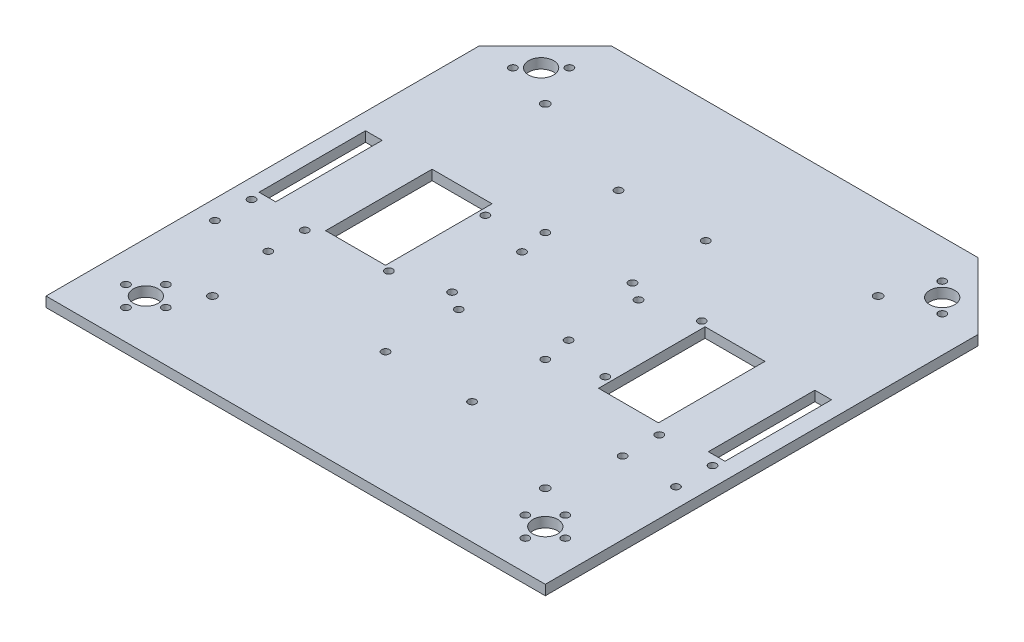
SolidWorks part; units mm, degrees
ref_plane "Plan de face" through (0, 0, 0) normal (0, 0, 1) x (1, 0, 0)
ref_plane "Plan de dessus" through (0, 0, 0) normal (0, 1, 0) x (1, 0, 0)
ref_plane "Plan de droite" through (0, 0, 0) normal (1, 0, 0) x (0, 0, -1)
sketch "Esquisse1" plane through (0, 0, 0) normal (0, 1, 0) x (1, 0, 0)
  line L0 (-150, 0) -> (-150, 260)
  line L2 (150, 0) -> (150, 260)
  line L3 (-150, 260) -> (-110, 260) construction
  line L4 (-110, 260) -> (-110, 300) construction
  line L5 (150, 260) -> (110, 260) construction
  line L6 (110, 260) -> (110, 300) construction
  line L8 (-150, 260) -> (-110, 300)
  line L9 (-110, 300) -> (110, 300)
  line L10 (0, 0) -> (0, 300) construction
  line L11 (110, 300) -> (150, 260)
  line L12 (-150, 0) -> (-120, 0) construction
  line L13 (-120, 18) -> (-120, 0) construction
  line L14 (150, 0) -> (120, 0) construction
  line L15 (120, 18) -> (120, 0) construction
  line L17 (-150, 260) -> (-120, 260) construction
  line L18 (-120, 260) -> (-120, 267.5) construction
  line L19 (150, 260) -> (120, 260) construction
  line L20 (120, 260) -> (120, 268.5) construction
  line L21 (-120, 267.5) -> (-111.5147, 275.9853) construction
  line L22 (-120, 267.5) -> (-128.4853, 259.0147) construction
  line L23 (120, 268.5) -> (128.4853, 260.0147) construction
  line L24 (120, 268.5) -> (111.5147, 276.9853) construction
  line L25 (-150, 0) -> (150, 0) construction
  line L26 (120, 30) -> (120, 18) construction
  line L27 (120, 30) -> (120, 42) construction
  line L28 (-150, 0) -> (150, 0)
  line L29 (-120, 18) -> (-120, 30) construction
  line L30 (-120, 30) -> (-120, 42) construction
  line L32 (150, 150) -> (-150, 150) construction
  line L33 (-120, 30) -> (-108, 30) construction
  line L34 (-120, 30) -> (-132, 30) construction
  line L35 (120, 30) -> (132, 30) construction
  line L36 (120, 30) -> (108, 30) construction
  circle A2 centre (-120, 30) radius 7.5
  circle A4 centre (-120, 267.5) radius 7.5
  circle A5 centre (120, 268.5) radius 7.5
  circle A6 centre (-111.5147, 275.9853) radius 2.3
  circle A7 centre (-128.4853, 259.0147) radius 2.3
  circle A8 centre (111.5147, 276.9853) radius 2.3
  circle A9 centre (128.4853, 260.0147) radius 2.3
  circle A10 centre (120, 30) radius 7.5
  circle A11 centre (120, 42) radius 2.3
  circle A13 centre (-120, 42) radius 2.3
  circle A14 centre (-120, 18) radius 2.3
  circle A16 centre (-132, 30) radius 2.3
  circle A17 centre (-108, 30) radius 2.3
  circle A18 centre (108, 30) radius 2.3
  circle A19 centre (132, 30) radius 2.3
  circle A20 centre (120, 18) radius 2.3
extrude "Boss.-Extru.1" add sketch "Esquisse1" along normal blind 6
sketch "Esquisse7" plane through (0, 6, 0) normal (0, 1, 0) x (1, 0, 0)
  line L0 (0, 150) -> (-130, 150) construction
  line L1 (0, 0) -> (0, 300) construction
  line L2 (150, 150) -> (-150, 150) construction
  line L3 (-130, 150) -> (-130, 182)
  line L4 (-130, 182) -> (-140, 182)
  line L5 (-140, 182) -> (-140, 118)
  line L6 (-140, 118) -> (-130, 118)
  line L7 (-130, 118) -> (-130, 150)
extrude "Enlèv. mat.-Extru.9" cut sketch "Esquisse7" against normal blind 10.5
sketch "Esquisse6" plane through (0, 6, 0) normal (0, 1, 0) x (1, 0, 0)
  line L0 (-142.5, 116) -> (-134.5, 116) construction
  line L2 (-142.5, 116) -> (-142.5, 150) construction
  line L3 (-142.5, 116) -> (-142.5, 108) construction
  line L11 (-142.5, 108) -> (-134.5, 108) construction
  line L12 (-134.5, 108) -> (-134.5, 116) construction
  line L14 (-142.5, 150) -> (-150, 150) construction
  line L15 (-142.5, 116) -> (-102.5, 116) construction
  line L16 (-102.5, 116) -> (-102.5, 108) construction
  line L17 (-102.5, 108) -> (-110.5, 108) construction
  line L18 (-110.5, 108) -> (-110.5, 116) construction
  line L19 (-110.5, 116) -> (-134.5, 116) construction
  line L20 (-134.5, 116) -> (-134.5, 86) construction
  line L21 (-134.5, 86) -> (-142.5, 86) construction
  line L22 (-142.5, 86) -> (-142.5, 94) construction
  line L23 (-142.5, 94) -> (-134.5, 94) construction
  line L24 (-134.5, 94) -> (-134.5, 86) construction
  line L25 (-134.5, 86) -> (-110.5, 86) construction
  line L26 (-110.5, 86) -> (-110.5, 94) construction
  line L27 (-110.5, 94) -> (-102.5, 94) construction
  line L28 (-102.5, 94) -> (-102.5, 86) construction
  line L29 (-102.5, 86) -> (-110.5, 86) construction
  line L30 (-102.5, 94) -> (-110.5, 86) construction
  line L31 (-110.5, 94) -> (-102.5, 86) construction
  line L32 (-142.5, 94) -> (-134.5, 86) construction
  line L33 (-142.5, 86) -> (-134.5, 94) construction
  line L34 (-142.5, 116) -> (-134.5, 108) construction
  line L35 (-142.5, 108) -> (-134.5, 116) construction
  line L71 (-110.5, 116) -> (-102.5, 108) construction
  line L72 (-110.5, 108) -> (-102.5, 116) construction
  line L73 (-110.5, 116) -> (-110.5, 86) construction
  circle A20 centre (-138.5, 90) radius 2.3
  circle A21 centre (-138.5, 112) radius 2.3
  circle A22 centre (-106.5, 112) radius 2.3
  circle A23 centre (-106.5, 90) radius 2.3
  dimension "D1" = 7.5
  dimension "D2" = 34
sketch "Esquisse4" plane through (0, 6, 0) normal (0, 1, 0) x (1, 0, 0)
  line L0 (-150, 150) -> (-100, 150) construction
  line L8 (150, 150) -> (-150, 150) construction
  line L14 (-100, 150) -> (-100, 182)
  line L15 (-100, 250) -> (-100, 50) construction
  line L16 (-100, 150) -> (-100, 118)
  line L17 (-100, 118) -> (-64, 118)
  line L18 (-64, 118) -> (-64, 182)
  line L19 (-64, 182) -> (-100, 182)
sketch "Esquisse9" plane through (0, 6, 0) normal (0, 1, 0) x (1, 0, 0)
  line L0 (-150, 0) -> (150, 0) construction
  line L1 (150, 0) -> (150, 300) construction
  line L2 (150, 300) -> (-150, 300) construction
  line L3 (-150, 300) -> (-150, 0) construction
  line L5 (-150, 0) -> (-150, 300) construction
  line L6 (150, 0) -> (0, 0) construction
  line L7 (0, 0) -> (0, 50) construction
  line L8 (0, 0) -> (0, 300) construction
  line L9 (0, 50) -> (100, 50) construction
  line L10 (100, 50) -> (100, 250) construction
  line L11 (100, 250) -> (-100, 250) construction
  line L12 (-100, 250) -> (-100, 50) construction
  line L13 (-100, 50) -> (0, 50) construction
  line L18 (100, 250) -> (94.3431, 244.3431) construction
  line L21 (-150, 0) -> (150, 300) construction
  circle A0 centre (-100, 50) radius 2.5
  circle A1 centre (100, 50) radius 2.5
  circle A2 centre (100, 250) radius 2.5
  circle A3 centre (-100, 250) radius 2.5
  point P20 (0, 0)
extrude "Enlèv. mat.-Extru.10" cut sketch "Esquisse6" against normal blind 50
extrude "Enlèv. mat.-Extru.11" cut sketch "Esquisse4" against normal blind 50
sketch "Esquisse3" plane through (0, 6, 0) normal (0, 1, 0) x (1, 0, 0)
  line L6 (-150, 150) -> (-64, 150) construction
  line L7 (-64, 118) -> (-64, 182) construction
  line L8 (-64, 150) -> (-64, 178) construction
  line L9 (-64, 178) -> (-56, 178) construction
  line L10 (-56, 178) -> (-56, 170) construction
  line L11 (-56, 170) -> (-59, 170) construction
  line L16 (-64, 150) -> (-64, 112) construction
  line L17 (-64, 112) -> (-56, 112) construction
  line L25 (-56, 112) -> (-56, 120) construction
  line L26 (-64, 120) -> (-34, 120) construction
  line L27 (-56, 170) -> (-64, 178) construction
  line L28 (-64, 178) -> (-56, 178) construction
  line L29 (-56, 178) -> (-64, 170) construction
  line L30 (-34, 120) -> (-26, 120) construction
  line L31 (-56, 112) -> (-64, 120) construction
  line L32 (-64, 120) -> (-56, 120) construction
  line L33 (-56, 120) -> (-64, 112) construction
  line L37 (-26, 120) -> (-26, 128) construction
  line L38 (-26, 128) -> (-34, 128) construction
  line L39 (-34, 128) -> (-26, 120) construction
  line L43 (-26, 120) -> (-34, 120) construction
  line L55 (150, 150) -> (64, 150) construction
  line L56 (150, 150) -> (-150, 150) construction
  line L57 (64, 150) -> (64, 170) construction
  line L58 (34, 130) -> (26, 130) construction
  line L61 (64, 150) -> (64, 130) construction
  line L62 (64, 130) -> (59, 130) construction
  line L63 (59, 130) -> (59, 165) construction
  line L66 (59, 165) -> (39, 165) construction
  line L70 (39, 165) -> (39, 130) construction
  line L72 (39, 130) -> (34, 130) construction
  line L73 (34, 130) -> (34, 180) construction
  line L74 (34, 180) -> (64, 180) construction
  line L76 (64, 180) -> (64, 130) construction
  line L77 (-34, 120) -> (-26, 128) construction
  line L78 (26, 130) -> (26, 138) construction
  line L79 (-34, 120) -> (-34, 170) construction
  line L80 (-39, 170) -> (-34, 170) construction
  line L81 (-34, 170) -> (-26, 170) construction
  line L82 (-26, 170) -> (-26, 162) construction
  line L83 (-26, 162) -> (-34, 162) construction
  line L84 (-34, 162) -> (-26, 170) construction
  line L85 (-26, 170) -> (-34, 170) construction
  line L86 (-34, 170) -> (-26, 162) construction
  line L87 (26, 138) -> (34, 138) construction
  line L88 (-59, 170) -> (-59, 138) construction
  line L89 (-59, 138) -> (-39, 138) construction
  line L90 (-39, 138) -> (-39, 170) construction
  line L91 (34, 138) -> (26, 130) construction
  line L92 (26, 130) -> (26, 138) construction
  line L93 (26, 138) -> (34, 130) construction
  line L94 (34, 130) -> (34, 180) construction
  line L95 (34, 180) -> (26, 180) construction
  line L96 (26, 180) -> (26, 172) construction
  line L97 (26, 172) -> (34, 172) construction
  line L98 (34, 172) -> (26, 180) construction
  line L99 (26, 180) -> (26, 172) construction
  line L100 (26, 172) -> (34, 180) construction
  line L101 (64, 180) -> (64, 188) construction
  line L102 (64, 188) -> (56, 188) construction
  line L103 (56, 188) -> (56, 180) construction
  line L104 (56, 180) -> (64, 188) construction
  line L105 (64, 188) -> (56, 188) construction
  line L106 (56, 188) -> (64, 180) construction
  line L107 (64, 180) -> (64, 130) construction
  line L108 (64, 130) -> (64, 122) construction
  line L109 (64, 122) -> (56, 122) construction
  line L110 (56, 122) -> (56, 130) construction
  line L111 (56, 130) -> (59, 130) construction
  line L112 (64, 122) -> (56, 130) construction
  line L113 (56, 130) -> (56, 122) construction
  line L114 (56, 122) -> (64, 130) construction
  circle A8 centre (-60, 174) radius 2.3
  circle A10 centre (-60, 116) radius 2.3
  circle A12 centre (-30, 166) radius 2.3
  circle A13 centre (-30, 124) radius 2.3
  circle A14 centre (60, 184) radius 2.3
  circle A15 centre (30, 176) radius 2.3
  circle A16 centre (30, 134) radius 2.3
  circle A17 centre (60, 126) radius 2.3
mirror "Symétrie1" about plane through (0, 0, 0) normal (1, 0, 0) of "Enlèv. mat.-Extru.9"
mirror "Symétrie2" about plane through (0, 0, 0) normal (1, 0, 0) of "Enlèv. mat.-Extru.11"
mirror "Symétrie3" about plane through (0, 0, 0) normal (1, 0, 0) of "Enlèv. mat.-Extru.10"
extrude "Enlèv. mat.-Extru.12" cut sketch "Esquisse9" against normal blind 35
extrude "Enlèv. mat.-Extru.13" cut sketch "Esquisse3" against normal blind 35
sketch "Esquisse10" plane through (0, 6, 0) normal (0, 1, 0) x (1, 0, 0)
  line L0 (0, 150) -> (0, 205) construction
  line L1 (-37, 187) -> (-51.6, 187) construction
  line L2 (-37, 187) -> (-37, 223) construction
  line L3 (0, 113) -> (37, 113) construction
  line L4 (37, 113) -> (37, 77) construction
  line L5 (37, 77) -> (-23, 77) construction
  line L6 (-23, 77) -> (-23, 113) construction
  line L7 (-23, 113) -> (37, 113) construction
  line L8 (37, 113) -> (37, 69) construction
  line L9 (37, 69) -> (29, 69) construction
  line L10 (29, 69) -> (29, 77) construction
  line L11 (29, 77) -> (37, 69) construction
  line L12 (37, 69) -> (37, 77) construction
  line L13 (37, 77) -> (29, 69) construction
  line L14 (37, 113) -> (37, 121) construction
  line L15 (37, 121) -> (29, 121) construction
  line L16 (29, 121) -> (29, 113) construction
  line L17 (37, 95) -> (56.6, 95) construction
  line L18 (29, 69) -> (29, 77) construction
  line L19 (29, 113) -> (-23, 113) construction
  line L20 (29, 77) -> (-23, 77) construction
  line L21 (-23, 77) -> (-23, 69) construction
  line L22 (-23, 69) -> (-15, 69) construction
  line L23 (-15, 69) -> (-15, 77) construction
  line L24 (-37, 187) -> (-37, 179) construction
  line L25 (-37, 179) -> (-29, 179) construction
  line L26 (-15, 77) -> (-23, 69) construction
  line L27 (-23, 69) -> (-23, 77) construction
  line L28 (-23, 77) -> (-15, 69) construction
  line L29 (29, 113) -> (37, 121) construction
  line L30 (37, 121) -> (37, 113) construction
  line L31 (37, 113) -> (29, 121) construction
  line L32 (-23, 113) -> (-23, 121) construction
  line L33 (-23, 121) -> (-15, 121) construction
  line L34 (-15, 121) -> (-15, 113) construction
  line L35 (-29, 179) -> (-29, 187) construction
  line L36 (-37, 223) -> (23.4, 223) construction
  line L37 (23.4, 223) -> (23.4, 187) construction
  line L38 (23.4, 187) -> (-37, 187) construction
  line L39 (-37, 187) -> (23.4, 187) construction
  line L40 (23.4, 187) -> (23.4, 179) construction
  line L41 (23.4, 179) -> (15.4, 179) construction
  line L42 (0, 95) -> (37, 95) construction
  line L43 (-29, 187) -> (-37, 179) construction
  line L44 (-37, 179) -> (-37, 187) construction
  line L45 (-37, 187) -> (-29, 179) construction
  line L46 (-23, 121) -> (-15, 113) construction
  line L47 (0, 205) -> (-37, 205) construction
  line L48 (-15, 113) -> (-15, 121) construction
  line L49 (-15, 121) -> (-23, 113) construction
  line L50 (15.4, 179) -> (15.4, 187) construction
  line L51 (15.4, 187) -> (23.4, 179) construction
  line L52 (23.4, 179) -> (23.4, 187) construction
  line L53 (23.4, 187) -> (15.4, 179) construction
  line L54 (15.4, 179) -> (15.4, 187) construction
  line L55 (15.4, 187) -> (23.4, 187) construction
  line L56 (23.4, 187) -> (23.4, 223) construction
  line L57 (23.4, 223) -> (23.4, 231) construction
  line L58 (23.4, 231) -> (15.4, 231) construction
  line L59 (15.4, 231) -> (15.4, 223) construction
  line L60 (15.4, 223) -> (23.4, 231) construction
  line L61 (23.4, 231) -> (15.4, 231) construction
  line L62 (15.4, 231) -> (23.4, 223) construction
  line L73 (-52, 205) -> (-37, 205) construction
  line L78 (0, 0) -> (0, 300) construction
  line L79 (0, 150) -> (0, 95) construction
  line L80 (-37, 223) -> (-37, 231) construction
  line L83 (-20.6, 223) -> (-29, 223) construction
  line L84 (-29, 223) -> (-37, 231) construction
  line L85 (-37, 231) -> (-29, 231) construction
  line L89 (-29, 223) -> (-29, 231) construction
  line L90 (-29, 231) -> (-37, 223) construction
  circle A18 centre (-33, 227) radius 2.3
  circle A22 centre (-19, 73) radius 2.3
  circle A25 centre (33, 73) radius 2.3
  circle A26 centre (-33, 183) radius 2.3
  circle A29 centre (33, 117) radius 2.3
  circle A30 centre (-19, 117) radius 2.3
  circle A31 centre (19.4, 227) radius 2.3
  circle A32 centre (19.4, 183) radius 2.3
extrude "Enlèv. mat.-Extru.14" cut sketch "Esquisse10" against normal blind 10
sketch "Esquisse11" plane through (0, 6, 0) normal (0, 1, 0) x (1, 0, 0)
  line L0 (0, 150) -> (0, 185) construction
  line L1 (0, 0) -> (0, 300) construction
  line L2 (0, 185) -> (-30, 185) construction
  line L3 (-30, 185) -> (-30, 235) construction
  line L4 (-30, 185) -> (-30, 193) construction
  line L5 (0, 150) -> (0, 115) construction
  line L6 (0, 115) -> (30, 115) construction
  line L7 (30, 107) -> (30, 72) construction
  line L8 (30, 115) -> (30, 107) construction
  line L9 (-30, 223) -> (-38, 223) construction
  line L12 (-30, 213) -> (-38, 213) construction
  circle A7 centre (30, 97) radius 2.3
  circle A9 centre (30, 77) radius 2.3
  circle A11 centre (-30, 203) radius 2.3
  circle A13 centre (-30, 223) radius 2.3
  circle A17 centre (-30, 185) radius 2.3
  circle A18 centre (30, 115) radius 2.3
  circle A19 centre (-40, 223) radius 2.3
  circle A20 centre (-50, 223) radius 2.3
  circle A21 centre (40, 77) radius 2.3
  circle A22 centre (50, 77) radius 2.3
  dimension "D1" = 3
  dimension "D2" = 3
